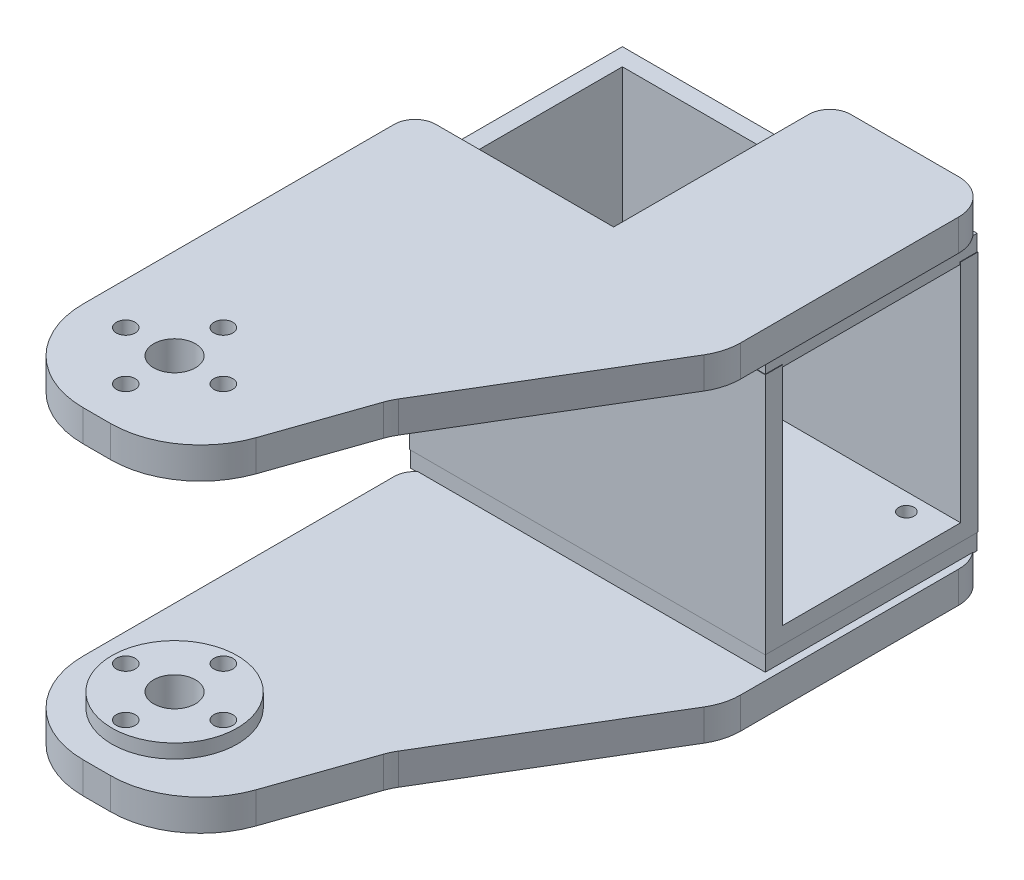
SolidWorks part; units mm, degrees
ref_plane "Front Plane" through (0, 0, 0) normal (0, 0, 1) x (1, 0, 0)
ref_plane "Top Plane" through (0, 0, 0) normal (0, 1, 0) x (1, 0, 0)
ref_plane "Right Plane" through (0, 0, 0) normal (1, 0, 0) x (0, 0, -1)
ref_plane "PY_p18_625" through (0, 18.625, 0) normal (0, 1, 0) x (1, 0, 0)
sketch "S_prism1" plane through (0, 18.625, 0) normal (0, 1, 0) x (1, 0, 0)
  line L0 (-0.1, -13) -> (3.8289, -13)
  line L1 (16.0129, -4.3379) -> (20.7288, 9.2202)
  line L2 (21.4248, 10.708) -> (37.8599, 38.0999)
  line L3 (39, 42.2159) -> (39, 73.5)
  line L4 (34, 78.5) -> (18.5, 78.5)
  line L5 (15.5, 75.5) -> (15.5, 47.5)
  line L6 (15.5, 47.5) -> (-10, 47.5)
  line L7 (-13, 44.5) -> (-13, -0.1)
  arc A0 (-13, -0.1) -> (-0.1, -13) centre (-0.1001, -0.1001) ccw
  arc A1 (3.8289, -13) -> (16.0129, -4.3379) centre (3.8289, -0.1) ccw
  arc A2 (20.7288, 9.2202) -> (21.4248, 10.708) centre (28.2833, 6.5929) cw
  arc A3 (37.8599, 38.0999) -> (39, 42.2159) centre (31, 42.2159) ccw
  arc A4 (39, 73.5) -> (34, 78.5) centre (33.9999, 73.4999) ccw
  arc A5 (18.5, 78.5) -> (15.5, 75.5) centre (18.5001, 75.4999) ccw
  arc A6 (-10, 47.5) -> (-13, 44.5) centre (-9.9999, 44.4999) ccw
extrude "Boss_1" add sketch "S_prism1" along normal blind 4.5
ref_plane "PY_m20_625" through (0, -20.625, 0) normal (0, 1, 0) x (1, 0, 0)
sketch "S_cyl2" plane through (0, -20.625, 0) normal (0, 1, 0) x (1, 0, 0)
  circle A0 centre (0, 0) radius 9
  dimension "D1_S_cyl2" = 18
extrude "Boss_2" add sketch "S_cyl2" along normal blind 2
ref_plane "PY_m25_125" through (0, -25.125, 0) normal (0, 1, 0) x (1, 0, 0)
sketch "S_prism3" plane through (0, -25.125, 0) normal (0, 1, 0) x (1, 0, 0)
  line L0 (-0.1, -13) -> (3.8289, -13)
  line L1 (16.0129, -4.3379) -> (20.7288, 9.2202)
  line L2 (21.4248, 10.708) -> (37.8599, 38.0999)
  line L3 (39, 42.2159) -> (39, 73.5)
  line L4 (34, 78.5) -> (18.5, 78.5)
  line L5 (15.5, 75.5) -> (15.5, 47.5)
  line L6 (15.5, 47.5) -> (-10, 47.5)
  line L7 (-13, 44.5) -> (-13, -0.1)
  arc A0 (-13, -0.1) -> (-0.1, -13) centre (-0.1001, -0.1001) ccw
  arc A1 (3.8289, -13) -> (16.0129, -4.3379) centre (3.8289, -0.1) ccw
  arc A2 (20.7288, 9.2202) -> (21.4248, 10.708) centre (28.2833, 6.5929) cw
  arc A3 (37.8599, 38.0999) -> (39, 42.2159) centre (31, 42.2159) ccw
  arc A4 (39, 73.5) -> (34, 78.5) centre (33.9999, 73.4999) ccw
  arc A5 (18.5, 78.5) -> (15.5, 75.5) centre (18.5001, 75.4999) ccw
  arc A6 (-10, 47.5) -> (-13, 44.5) centre (-9.9999, 44.4999) ccw
extrude "Boss_3" add sketch "S_prism3" along normal blind 4.5
ref_plane "PZ_m77_260" through (0, 0, -77.26) normal (0, 0, 1) x (1, 0, 0)
sketch "S_box4" plane through (0, 0, -77.26) normal (0, 0, 1) x (1, 0, 0)
  line L0 (-13.01, -18.4) -> (-10.51, -18.4)
  line L1 (-10.51, -18.4) -> (-10.51, 16.4)
  line L2 (-10.51, 16.4) -> (-13.01, 16.4)
  line L3 (-13.01, 16.4) -> (-13.01, -18.4)
  dimension "P1" = 13.01
  dimension "P2" = 18.4
  dimension "P3" = 10.51
  dimension "P4" = 18.4
  dimension "P5" = 10.51
  dimension "P6" = 16.4
  dimension "P7" = 13.01
  dimension "P8" = 16.4
extrude "Boss_4" add sketch "S_box4" along normal blind 30.52
sketch "S_box5" plane through (0, 0, -77.26) normal (0, 0, 1) x (1, 0, 0)
  line L0 (-13.01, -18.4) -> (38.01, -18.4)
  line L1 (38.01, -18.4) -> (38.01, 16.4)
  line L2 (38.01, 16.4) -> (-13.01, 16.4)
  line L3 (-13.01, 16.4) -> (-13.01, -18.4)
  dimension "P1" = 13.01
  dimension "P2" = 18.4
  dimension "P3" = 38.01
  dimension "P4" = 18.4
  dimension "P5" = 38.01
  dimension "P6" = 16.4
  dimension "P7" = 13.01
  dimension "P8" = 16.4
extrude "Boss_5" add sketch "S_box5" along normal blind 2.5
ref_plane "PZ_m49_240" through (0, 0, -49.24) normal (0, 0, 1) x (1, 0, 0)
sketch "S_box6" plane through (0, 0, -49.24) normal (0, 0, 1) x (1, 0, 0)
  line L0 (-13.01, -18.4) -> (38.01, -18.4)
  line L1 (38.01, -18.4) -> (38.01, 16.4)
  line L2 (38.01, 16.4) -> (-13.01, 16.4)
  line L3 (-13.01, 16.4) -> (-13.01, -18.4)
  dimension "P1" = 13.01
  dimension "P2" = 18.4
  dimension "P3" = 38.01
  dimension "P4" = 18.4
  dimension "P5" = 38.01
  dimension "P6" = 16.4
  dimension "P7" = 13.01
  dimension "P8" = 16.4
extrude "Boss_6" add sketch "S_box6" along normal blind 2.5
sketch "S_box7" plane through (0, 0, -77.26) normal (0, 0, 1) x (1, 0, 0)
  line L0 (-13.01, -18.4) -> (38.01, -18.4)
  line L1 (38.01, -18.4) -> (38.01, -16)
  line L2 (38.01, -16) -> (-13.01, -16)
  line L3 (-13.01, -16) -> (-13.01, -18.4)
  dimension "P1" = 13.01
  dimension "P2" = 18.4
  dimension "P3" = 38.01
  dimension "P4" = 18.4
  dimension "P5" = 38.01
  dimension "P6" = 16
  dimension "P7" = 13.01
  dimension "P8" = 16
extrude "Boss_7" add sketch "S_box7" along normal blind 30.52
ref_plane "PZ_m77_190" through (0, 0, -77.19) normal (0, 0, 1) x (1, 0, 0)
sketch "S_box8" plane through (0, 0, -77.19) normal (0, 0, 1) x (1, 0, 0)
  line L0 (15.5, 16.05) -> (37.94, 16.05)
  line L1 (37.94, 16.05) -> (37.94, 18.725)
  line L2 (37.94, 18.725) -> (15.5, 18.725)
  line L3 (15.5, 18.725) -> (15.5, 16.05)
  dimension "P1" = 15.5
  dimension "P2" = 16.05
  dimension "P3" = 37.94
  dimension "P4" = 16.05
  dimension "P5" = 37.94
  dimension "P6" = 18.725
  dimension "P7" = 15.5
  dimension "P8" = 18.725
extrude "Boss_8" add sketch "S_box8" along normal blind 30.38
ref_plane "PZ_m48_500" through (0, 0, -48.5) normal (0, 0, 1) x (1, 0, 0)
sketch "S_box9" plane through (0, 0, -48.5) normal (0, 0, 1) x (1, 0, 0)
  line L0 (-12.94, 16.05) -> (15.53, 16.05)
  line L1 (15.53, 16.05) -> (15.53, 18.725)
  line L2 (15.53, 18.725) -> (-12.94, 18.725)
  line L3 (-12.94, 18.725) -> (-12.94, 16.05)
  dimension "P1" = 12.94
  dimension "P2" = 16.05
  dimension "P3" = 15.53
  dimension "P4" = 16.05
  dimension "P5" = 15.53
  dimension "P6" = 18.725
  dimension "P7" = 12.94
  dimension "P8" = 18.725
extrude "Boss_9" add sketch "S_box9" along normal blind 1.69
sketch "S_box10" plane through (0, 0, -77.19) normal (0, 0, 1) x (1, 0, 0)
  line L0 (15.5, -20.725) -> (37.94, -20.725)
  line L1 (37.94, -20.725) -> (37.94, -18.3)
  line L2 (37.94, -18.3) -> (15.5, -18.3)
  line L3 (15.5, -18.3) -> (15.5, -20.725)
  dimension "P1" = 15.5
  dimension "P2" = 20.725
  dimension "P3" = 37.94
  dimension "P4" = 20.725
  dimension "P5" = 37.94
  dimension "P6" = 18.3
  dimension "P7" = 15.5
  dimension "P8" = 18.3
extrude "Boss_10" add sketch "S_box10" along normal blind 30.38
sketch "S_box11" plane through (0, 0, -48.5) normal (0, 0, 1) x (1, 0, 0)
  line L0 (-12.94, -20.725) -> (15.53, -20.725)
  line L1 (15.53, -20.725) -> (15.53, -18.3)
  line L2 (15.53, -18.3) -> (-12.94, -18.3)
  line L3 (-12.94, -18.3) -> (-12.94, -20.725)
  dimension "P1" = 12.94
  dimension "P2" = 20.725
  dimension "P3" = 15.53
  dimension "P4" = 20.725
  dimension "P5" = 15.53
  dimension "P6" = 18.3
  dimension "P7" = 12.94
  dimension "P8" = 18.3
extrude "Boss_11" add sketch "S_box11" along normal blind 1.69
ref_plane "PY_p18_525" through (0, 18.525, 0) normal (0, 1, 0) x (1, 0, 0)
sketch "S_hole12" plane through (0, 18.525, 0) normal (0, 1, 0) x (1, 0, 0)
  circle A0 centre (0, 0) radius 3
  dimension "D1_S_hole12" = 6
extrude "Hole_12" cut sketch "S_hole12" along normal blind 4.7
sketch "S_hole13" plane through (0, 18.525, 0) normal (0, 1, 0) x (1, 0, 0)
  circle A0 centre (7, 0) radius 1.35
  dimension "D1_S_hole13" = 2.7
  dimension "P2" = 7
extrude "Hole_13" cut sketch "S_hole13" along normal blind 4.7
sketch "S_hole14" plane through (0, 18.525, 0) normal (0, 1, 0) x (1, 0, 0)
  circle A0 centre (0, -7) radius 1.35
  dimension "D1_S_hole14" = 2.7
  dimension "P2" = 7
extrude "Hole_14" cut sketch "S_hole14" along normal blind 4.7
sketch "S_hole15" plane through (0, 18.525, 0) normal (0, 1, 0) x (1, 0, 0)
  circle A0 centre (-7, 0) radius 1.35
  dimension "D1_S_hole15" = 2.7
  dimension "P2" = 7
extrude "Hole_15" cut sketch "S_hole15" along normal blind 4.7
sketch "S_hole16" plane through (0, 18.525, 0) normal (0, 1, 0) x (1, 0, 0)
  circle A0 centre (0, 7) radius 1.35
  dimension "D1_S_hole16" = 2.7
  dimension "P2" = 7
extrude "Hole_16" cut sketch "S_hole16" along normal blind 4.7
ref_plane "PY_m25_225" through (0, -25.225, 0) normal (0, 1, 0) x (1, 0, 0)
sketch "S_hole17" plane through (0, -25.225, 0) normal (0, 1, 0) x (1, 0, 0)
  circle A0 centre (0, 0) radius 3
  dimension "D1_S_hole17" = 6
extrude "Hole_17" cut sketch "S_hole17" along normal blind 6.7
sketch "S_hole18" plane through (0, -25.225, 0) normal (0, 1, 0) x (1, 0, 0)
  circle A0 centre (7, 0) radius 1.35
  dimension "D1_S_hole18" = 2.7
  dimension "P2" = 7
extrude "Hole_18" cut sketch "S_hole18" along normal blind 6.7
sketch "S_hole19" plane through (0, -25.225, 0) normal (0, 1, 0) x (1, 0, 0)
  circle A0 centre (0, -7) radius 1.35
  dimension "D1_S_hole19" = 2.7
  dimension "P2" = 7
extrude "Hole_19" cut sketch "S_hole19" along normal blind 6.7
sketch "S_hole20" plane through (0, -25.225, 0) normal (0, 1, 0) x (1, 0, 0)
  circle A0 centre (-7, 0) radius 1.35
  dimension "D1_S_hole20" = 2.7
  dimension "P2" = 7
extrude "Hole_20" cut sketch "S_hole20" along normal blind 6.7
sketch "S_hole21" plane through (0, -25.225, 0) normal (0, 1, 0) x (1, 0, 0)
  circle A0 centre (0, 7) radius 1.35
  dimension "D1_S_hole21" = 2.7
  dimension "P2" = 7
extrude "Hole_21" cut sketch "S_hole21" along normal blind 6.7
ref_plane "PY_m18_500" through (0, -18.5, 0) normal (0, 1, 0) x (1, 0, 0)
sketch "S_hole22" plane through (0, -18.5, 0) normal (0, 1, 0) x (1, 0, 0)
  circle A0 centre (0, 62) radius 11
  dimension "D1_S_hole22" = 22
  dimension "P2" = 62
extrude "Hole_22" cut sketch "S_hole22" along normal blind 2.6
sketch "S_hole23" plane through (0, -18.5, 0) normal (0, 1, 0) x (1, 0, 0)
  circle A0 centre (8.3, 51.75) radius 1.1
  dimension "D1_S_hole23" = 2.2
  dimension "P2" = 8.3
  dimension "P3" = 51.75
extrude "Hole_23" cut sketch "S_hole23" along normal blind 2.6
sketch "S_hole24" plane through (0, -18.5, 0) normal (0, 1, 0) x (1, 0, 0)
  circle A0 centre (32.75, 72.25) radius 1.1
  dimension "D1_S_hole24" = 2.2
  dimension "P2" = 32.75
  dimension "P3" = 72.25
extrude "Hole_24" cut sketch "S_hole24" along normal blind 2.6
sketch "S_hole25" plane through (0, -18.5, 0) normal (0, 1, 0) x (1, 0, 0)
  circle A0 centre (32.75, 51.75) radius 1.1
  dimension "D1_S_hole25" = 2.2
  dimension "P2" = 32.75
  dimension "P3" = 51.75
extrude "Hole_25" cut sketch "S_hole25" along normal blind 2.6
sketch "S_hole26" plane through (0, -25.225, 0) normal (0, 1, 0) x (1, 0, 0)
  circle A0 centre (32.75, 72.25) radius 2.5
  dimension "D1_S_hole26" = 5
  dimension "P2" = 32.75
  dimension "P3" = 72.25
extrude "Hole_26" cut sketch "S_hole26" along normal blind 6.775
sketch "S_hole27" plane through (0, -25.225, 0) normal (0, 1, 0) x (1, 0, 0)
  circle A0 centre (32.75, 51.75) radius 2.5
  dimension "D1_S_hole27" = 5
  dimension "P2" = 32.75
  dimension "P3" = 51.75
extrude "Hole_27" cut sketch "S_hole27" along normal blind 6.775
equation "\"plate_t\" = 3"
equation "\"clearance\" = 0.4"
